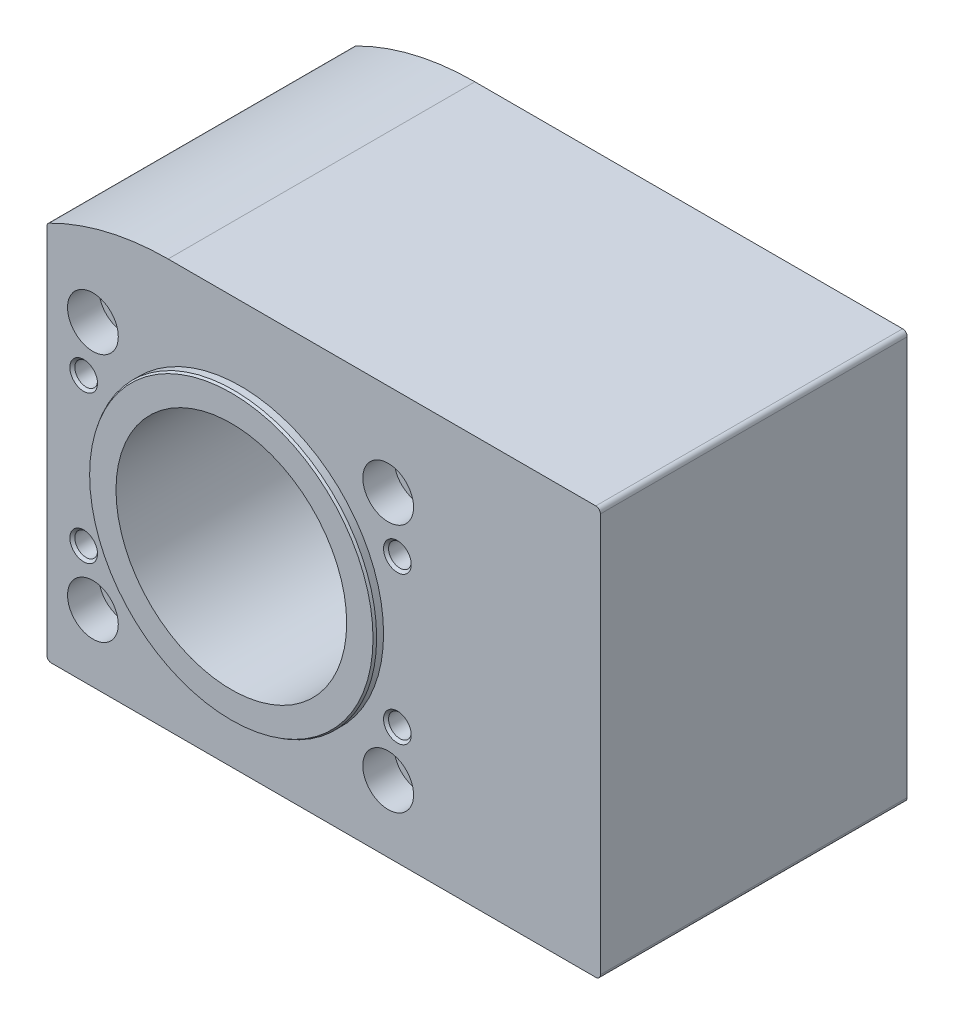
SolidWorks part; units mm, degrees
material "201.0-T43 Insulated Mold Casting (SS)"
ref_plane "Ebene vorne" through (0, 0, 0) normal (0, 0, 1) x (1, 0, 0)
ref_plane "Ebene oben" through (0, 0, 0) normal (0, 1, 0) x (1, 0, 0)
ref_plane "Ebene rechts" through (0, 0, 0) normal (1, 0, 0) x (0, 0, -1)
sketch "Skizze1" plane through (0, 0, 0) normal (0, 0, 1) x (1, 0, 0)
  line L0 (-42, 39.9591) -> (-42, -40.5)
  line L1 (-41, -41.5) -> (77, -41.5)
  line L2 (78, -40.5) -> (78, 46)
  line L3 (77, 47) -> (-15.7, 47)
  arc A0 (-42, -40.5) -> (-41, -41.5) centre (-41, -40.5) ccw
  arc A1 (77, -41.5) -> (78, -40.5) centre (77, -40.5) ccw
  arc A2 (78, 46) -> (77, 47) centre (77, 46) ccw
  arc A3 (-15.7, 47) -> (-41.4518, 40.8512) centre (-15.7, -10) ccw
  arc A4 (-41.4518, 40.8512) -> (-42, 39.9591) centre (-41, 39.9591) ccw
extrude "Linear austragen1" add sketch "Skizze1" along normal blind 66.5
sketch "Skizze2" plane through (0, 0, 0) normal (1, 0, 0) x (0, 0, -1)
  line L0 (-68.5, 0) -> (-68.5, 30.7113)
  line L1 (-68.5, 30.7113) -> (-68, 31)
  line L2 (-68, 31) -> (1.5, 31)
  line L3 (1.5, 31) -> (2, 30.7113)
  line L4 (2, 30.7113) -> (2, 0)
  line L5 (2, 0) -> (-68.5, 0)
  line L6 (2, 0) -> (-68.5, 0) construction
revolve "Rotation1" add sketch "Skizze2" angle 360 about L6 reverse direction yes
ref_plane "Ebene1" through (0, 0, -2) normal (0, 0, 1) x (1, 0, 0)
sketch "Skizze3" plane through (0, 0, -2) normal (0, 0, 1) x (1, 0, 0)
  circle A0 centre (0, 0) radius 25
extrude "Linear austragen2" cut sketch "Skizze3" along normal blind 70.5
ref_plane "Ebene2" through (-32, 0, 0) normal (1, 0, 0) x (0, 0, -1)
sketch "Skizze4" plane through (-32, 0, 0) normal (1, 0, 0) x (0, 0, -1)
  line L0 (-68.5, 27) -> (-68.5, 32.5)
  line L1 (-68.5, 32.5) -> (-59.7, 32.5)
  line L2 (-59.7, 32.5) -> (-59.7, 30.3)
  line L3 (-59.7, 30.3) -> (-6.8, 30.3)
  line L4 (-6.8, 30.3) -> (-6.8, 32.5)
  line L5 (-6.8, 32.5) -> (2, 32.5)
  line L6 (2, 32.5) -> (2, 27)
  line L7 (2, 27) -> (-68.5, 27)
  line L8 (2, 27) -> (-68.5, 27) construction
revolve "Schnitt-Rotation1" cut sketch "Skizze4" angle 360 about L8 reverse direction yes
sketch "Skizze5" plane through (-32, 0, 0) normal (1, 0, 0) x (0, 0, -1)
  line L0 (-68.5, -27) -> (-68.5, -21.5)
  line L1 (-68.5, -21.5) -> (-59.7, -21.5)
  line L2 (-59.7, -21.5) -> (-59.7, -23.7)
  line L3 (-59.7, -23.7) -> (-6.8, -23.7)
  line L4 (-6.8, -23.7) -> (-6.8, -21.5)
  line L5 (-6.8, -21.5) -> (2, -21.5)
  line L6 (2, -21.5) -> (2, -27)
  line L7 (2, -27) -> (-68.5, -27)
  line L8 (2, -27) -> (-68.5, -27) construction
revolve "Schnitt-Rotation2" cut sketch "Skizze5" angle 360 about L8 reverse direction yes
ref_plane "Ebene3" through (32, 0, 0) normal (1, 0, 0) x (0, 0, -1)
sketch "Skizze6" plane through (32, 0, 0) normal (1, 0, 0) x (0, 0, -1)
  line L0 (-68.5, -27) -> (-68.5, -21.5)
  line L1 (-68.5, -21.5) -> (-59.7, -21.5)
  line L2 (-59.7, -21.5) -> (-59.7, -23.7)
  line L3 (-59.7, -23.7) -> (-6.8, -23.7)
  line L4 (-6.8, -23.7) -> (-6.8, -21.5)
  line L5 (-6.8, -21.5) -> (2, -21.5)
  line L6 (2, -21.5) -> (2, -27)
  line L7 (2, -27) -> (-68.5, -27)
  line L8 (2, -27) -> (-68.5, -27) construction
revolve "Schnitt-Rotation3" cut sketch "Skizze6" angle 360 about L8 reverse direction yes
sketch "Skizze7" plane through (32, 0, 0) normal (1, 0, 0) x (0, 0, -1)
  line L0 (-68.5, 27) -> (-68.5, 32.5)
  line L1 (-68.5, 32.5) -> (-59.7, 32.5)
  line L2 (-59.7, 32.5) -> (-59.7, 30.3)
  line L3 (-59.7, 30.3) -> (-6.8, 30.3)
  line L4 (-6.8, 30.3) -> (-6.8, 32.5)
  line L5 (-6.8, 32.5) -> (2, 32.5)
  line L6 (2, 32.5) -> (2, 27)
  line L7 (2, 27) -> (-68.5, 27)
  line L8 (2, 27) -> (-68.5, 27) construction
revolve "Schnitt-Rotation4" cut sketch "Skizze7" angle 360 about L8 reverse direction yes
ref_plane "Ebene4" through (34, 0, 0) normal (1, 0, 0) x (0, 0, -1)
sketch "Skizze8" plane through (34, 0, 0) normal (1, 0, 0) x (0, 0, -1)
  line L0 (-18.5194, 16) -> (-17.1, 18.4585)
  line L1 (-17.1, 18.4585) -> (-0.5415, 18.4585)
  line L2 (-0.5415, 18.4585) -> (0, 19)
  line L3 (0, 19) -> (0, 16)
  line L4 (0, 16) -> (-18.5194, 16)
  line L5 (0, 16) -> (-18.5194, 16) construction
revolve "Schnitt-Rotation5" cut sketch "Skizze8" angle 360 about L5 reverse direction yes
cosmetic thread "Gewindedarstellung1" parameters "D1"=12, "D2"=6
sketch "Skizze9" plane through (34, 0, 0) normal (1, 0, 0) x (0, 0, -1)
  line L0 (-18.5194, -16) -> (-17.1, -13.5415)
  line L1 (-17.1, -13.5415) -> (-0.5415, -13.5415)
  line L2 (-0.5415, -13.5415) -> (0, -13)
  line L3 (0, -13) -> (0, -16)
  line L4 (0, -16) -> (-18.5194, -16)
  line L5 (0, -16) -> (-18.5194, -16) construction
revolve "Schnitt-Rotation6" cut sketch "Skizze9" angle 360 about L5 reverse direction yes
cosmetic thread "Gewindedarstellung2" parameters "D1"=12, "D2"=6
ref_plane "Ebene5" through (-34, 0, 0) normal (1, 0, 0) x (0, 0, -1)
sketch "Skizze10" plane through (-34, 0, 0) normal (1, 0, 0) x (0, 0, -1)
  line L0 (-18.5194, 16) -> (-17.1, 18.4585)
  line L1 (-17.1, 18.4585) -> (-0.5415, 18.4585)
  line L2 (-0.5415, 18.4585) -> (0, 19)
  line L3 (0, 19) -> (0, 16)
  line L4 (0, 16) -> (-18.5194, 16)
  line L5 (0, 16) -> (-18.5194, 16) construction
revolve "Schnitt-Rotation7" cut sketch "Skizze10" angle 360 about L5 reverse direction yes
cosmetic thread "Gewindedarstellung3" parameters "D1"=12, "D2"=6
sketch "Skizze11" plane through (-34, 0, 0) normal (1, 0, 0) x (0, 0, -1)
  line L0 (-18.5194, -16) -> (-17.1, -13.5415)
  line L1 (-17.1, -13.5415) -> (-0.5415, -13.5415)
  line L2 (-0.5415, -13.5415) -> (0, -13)
  line L3 (0, -13) -> (0, -16)
  line L4 (0, -16) -> (-18.5194, -16)
  line L5 (0, -16) -> (-18.5194, -16) construction
revolve "Schnitt-Rotation8" cut sketch "Skizze11" angle 360 about L5 reverse direction yes
cosmetic thread "Gewindedarstellung4" parameters "D1"=12, "D2"=6
sketch "Skizze12" plane through (-34, 0, 0) normal (1, 0, 0) x (0, 0, -1)
  line L0 (-66.5, 16) -> (-66.5, 19)
  line L1 (-66.5, 19) -> (-65.9585, 18.4585)
  line L2 (-65.9585, 18.4585) -> (-49.4, 18.4585)
  line L3 (-49.4, 18.4585) -> (-47.9806, 16)
  line L4 (-47.9806, 16) -> (-66.5, 16)
  line L5 (-47.9806, 16) -> (-66.5, 16) construction
revolve "Schnitt-Rotation9" cut sketch "Skizze12" angle 360 about L5 reverse direction yes
cosmetic thread "Gewindedarstellung5" parameters "D1"=12, "D2"=6
sketch "Skizze13" plane through (-34, 0, 0) normal (1, 0, 0) x (0, 0, -1)
  line L0 (-66.5, -16) -> (-66.5, -13)
  line L1 (-66.5, -13) -> (-65.9585, -13.5415)
  line L2 (-65.9585, -13.5415) -> (-49.4, -13.5415)
  line L3 (-49.4, -13.5415) -> (-47.9806, -16)
  line L4 (-47.9806, -16) -> (-66.5, -16)
  line L5 (-47.9806, -16) -> (-66.5, -16) construction
revolve "Schnitt-Rotation10" cut sketch "Skizze13" angle 360 about L5 reverse direction yes
cosmetic thread "Gewindedarstellung6" parameters "D1"=12, "D2"=6
sketch "Skizze14" plane through (34, 0, 0) normal (1, 0, 0) x (0, 0, -1)
  line L0 (-66.5, 16) -> (-66.5, 19)
  line L1 (-66.5, 19) -> (-65.9585, 18.4585)
  line L2 (-65.9585, 18.4585) -> (-49.4, 18.4585)
  line L3 (-49.4, 18.4585) -> (-47.9806, 16)
  line L4 (-47.9806, 16) -> (-66.5, 16)
  line L5 (-47.9806, 16) -> (-66.5, 16) construction
revolve "Schnitt-Rotation11" cut sketch "Skizze14" angle 360 about L5 reverse direction yes
cosmetic thread "Gewindedarstellung7" parameters "D1"=12, "D2"=6
sketch "Skizze15" plane through (34, 0, 0) normal (1, 0, 0) x (0, 0, -1)
  line L0 (-66.5, -16) -> (-66.5, -13)
  line L1 (-66.5, -13) -> (-65.9585, -13.5415)
  line L2 (-65.9585, -13.5415) -> (-49.4, -13.5415)
  line L3 (-49.4, -13.5415) -> (-47.9806, -16)
  line L4 (-47.9806, -16) -> (-66.5, -16)
  line L5 (-47.9806, -16) -> (-66.5, -16) construction
revolve "Schnitt-Rotation12" cut sketch "Skizze15" angle 360 about L5 reverse direction yes
cosmetic thread "Gewindedarstellung8" parameters "D1"=12, "D2"=6
ref_plane "Ebene6" through (0, 0, 66.5) normal (0, 0, 1) x (1, 0, 0)
ref_plane "Ebene7" through (0, 0, 0) normal (0, 0, 1) x (1, 0, 0)
ref_plane "Ebene8" through (0, 0, 6.8) normal (0, 0, 1) x (1, 0, 0)
ref_plane "ANBAU XY" through (0, 0, 0) normal (0, 0, 1) x (1, 0, 0)
ref_plane "ANBAU XZ" through (0, 0, 0) normal (0, -1, 0) x (1, 0, 0)
ref_plane "ANBAU YZ" through (0, 0, 0) normal (1, 0, 0) x (0, 0, -1)
ref_axis "ANBAU X" through (-80.9, 0, 0) along (1, 0, 0)
ref_axis "ANBAU Y" through (0, -50, 0) along (0, 1, 0)
ref_axis "ANBAU Z" through (0, 0, 80.9) along (0, 0, -1)
sketch3d "ANBAU"
  point P0 (0, 0, 0)
ref_plane "EAMK XY" through (0, 0, 0) normal (0, 0, 1) x (1, 0, 0)
ref_plane "EAMK XZ" through (0, 0, 0) normal (0, -1, 0) x (1, 0, 0)
ref_plane "EAMK YZ" through (0, 0, 0) normal (1, 0, 0) x (0, 0, -1)
ref_axis "EAMK X" through (-80.9, 0, 0) along (1, 0, 0)
ref_axis "EAMK Y" through (0, -50, 0) along (0, 1, 0)
ref_axis "EAMK Z" through (0, 0, 80.9) along (0, 0, -1)
sketch3d "EAMK"
  point P0 (0, 0, 0)
ref_plane "ZYL_SCHRAUBE_1 1 XY" through (0, 0, 6.8) normal (0, 0, -1) x (-1, 0, 0)
ref_plane "ZYL_SCHRAUBE_1 1 XZ" through (0, 27, 0) normal (0, 1, 0) x (-1, 0, 0)
ref_plane "ZYL_SCHRAUBE_1 1 YZ" through (-32, 0, 0) normal (1, 0, 0) x (0, 0, -1)
ref_axis "ZYL_SCHRAUBE_1 1 X" through (-80.9, 27, 6.8) along (1, 0, 0)
ref_axis "ZYL_SCHRAUBE_1 1 Y" through (-32, 50, 6.8) along (0, -1, 0)
ref_axis "ZYL_SCHRAUBE_1 1 Z" through (-32, 27, -80.9) along (0, 0, 1)
sketch3d "ZYL_SCHRAUBE_1 1"
  point P0 (-32, 27, 6.8)
ref_plane "ZYL_SCHRAUBE_1 2 XY" through (0, 0, 6.8) normal (0, 0, -1) x (-1, 0, 0)
ref_plane "ZYL_SCHRAUBE_1 2 XZ" through (0, 27, 0) normal (0, 1, 0) x (-1, 0, 0)
ref_plane "ZYL_SCHRAUBE_1 2 YZ" through (32, 0, 0) normal (1, 0, 0) x (0, 0, -1)
ref_axis "ZYL_SCHRAUBE_1 2 X" through (-80.9, 27, 6.8) along (1, 0, 0)
ref_axis "ZYL_SCHRAUBE_1 2 Y" through (32, 50, 6.8) along (0, -1, 0)
ref_axis "ZYL_SCHRAUBE_1 2 Z" through (32, 27, -80.9) along (0, 0, 1)
sketch3d "ZYL_SCHRAUBE_1 2"
  point P0 (32, 27, 6.8)
ref_plane "ZYL_SCHRAUBE_1 3 XY" through (0, 0, 6.8) normal (0, 0, -1) x (-1, 0, 0)
ref_plane "ZYL_SCHRAUBE_1 3 XZ" through (0, -27, 0) normal (0, 1, 0) x (-1, 0, 0)
ref_plane "ZYL_SCHRAUBE_1 3 YZ" through (-32, 0, 0) normal (1, 0, 0) x (0, 0, -1)
ref_axis "ZYL_SCHRAUBE_1 3 X" through (-80.9, -27, 6.8) along (1, 0, 0)
ref_axis "ZYL_SCHRAUBE_1 3 Y" through (-32, 50, 6.8) along (0, -1, 0)
ref_axis "ZYL_SCHRAUBE_1 3 Z" through (-32, -27, -80.9) along (0, 0, 1)
sketch3d "ZYL_SCHRAUBE_1 3"
  point P0 (-32, -27, 6.8)
ref_plane "ZYL_SCHRAUBE_1 4 XY" through (0, 0, 6.8) normal (0, 0, -1) x (-1, 0, 0)
ref_plane "ZYL_SCHRAUBE_1 4 XZ" through (0, -27, 0) normal (0, 1, 0) x (-1, 0, 0)
ref_plane "ZYL_SCHRAUBE_1 4 YZ" through (32, 0, 0) normal (1, 0, 0) x (0, 0, -1)
ref_axis "ZYL_SCHRAUBE_1 4 X" through (-80.9, -27, 6.8) along (1, 0, 0)
ref_axis "ZYL_SCHRAUBE_1 4 Y" through (32, 50, 6.8) along (0, -1, 0)
ref_axis "ZYL_SCHRAUBE_1 4 Z" through (32, -27, -80.9) along (0, 0, 1)
sketch3d "ZYL_SCHRAUBE_1 4"
  point P0 (32, -27, 6.8)
